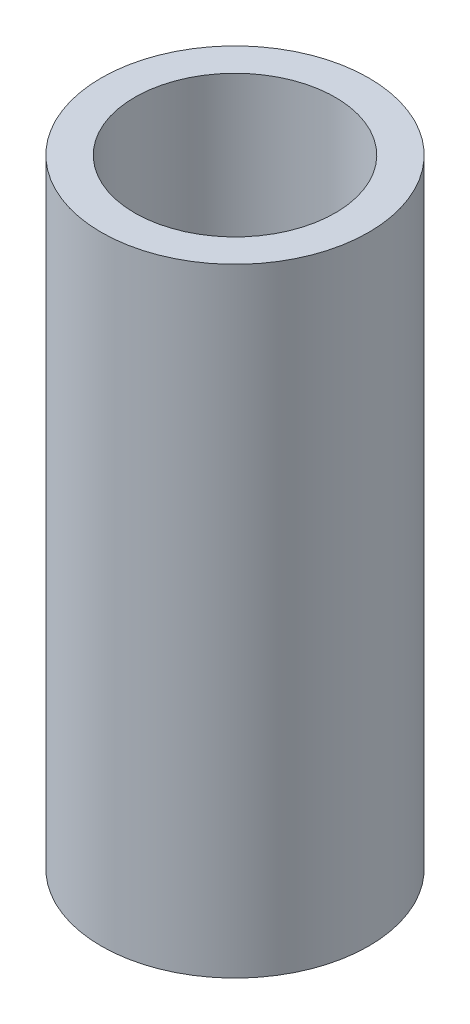
SolidWorks part; units mm, degrees
ref_plane "Front Plane" through (0, 0, 0) normal (0, 0, 1) x (1, 0, 0)
ref_plane "Top Plane" through (0, 0, 0) normal (0, 1, 0) x (1, 0, 0)
ref_plane "Right Plane" through (0, 0, 0) normal (1, 0, 0) x (0, 0, -1)
sketch "Sketch1" plane through (0, 0, 0) normal (0, 1, 0) x (1, 0, 0)
  circle A0 centre (0, 0) radius 10
  dimension "SLEEVE_OD" = 20
extrude "Boss-Extrude1" add sketch "Sketch1" along normal blind 46.2112
sketch "Sketch2" plane through (0, 0, 0) normal (0, 1, 0) x (1, 0, 0)
  circle A0 centre (0, 0) radius 7.495
  dimension "BORE_D" = 14.99
extrude "Cut-Extrude1" cut sketch "Sketch2" along normal through all
chamfer "Chamfer1" distance 1.7021 angle 59.038 rebuild error yes
